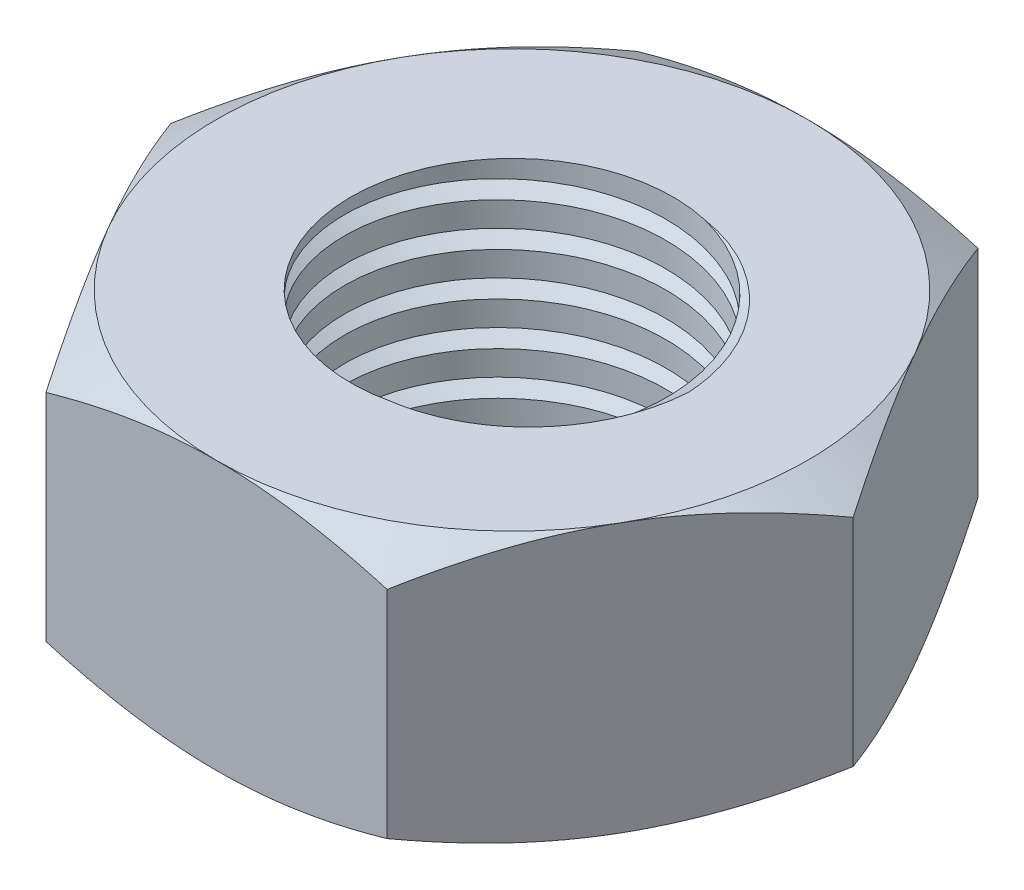
SolidWorks part; units mm, degrees
ref_plane "Front Plane" through (0, 0, 0) normal (0, 0, 1) x (1, 0, 0)
ref_plane "Top Plane" through (0, 0, 0) normal (0, 1, 0) x (1, 0, 0)
ref_plane "Right Plane" through (0, 0, 0) normal (1, 0, 0) x (0, 0, -1)
sketch "Sketch1" plane through (0, 0, 0) normal (0, 1, 0) x (1, 0, 0)
  line L0 (3.1754, 0) -> (1.5877, 2.75)
  line L1 (-3.1754, 0) -> (-1.5877, -2.75)
  line L2 (-1.5877, -2.75) -> (1.5877, -2.75)
  line L3 (1.5877, -2.75) -> (3.1754, 0)
  line L4 (1.5877, 2.75) -> (-1.5877, 2.75)
  line L5 (-1.5877, 2.75) -> (-3.1754, 0)
  circle A0 centre (0, 0) radius 2.75 construction
  dimension "D1" = 5.5
extrude "Boss-Extrude1" add sketch "Sketch1" along normal blind 2.5
sketch "Sketch2" plane through (0, 2.5, 0) normal (0, 1, 0) x (1, 0, 0)
  circle A0 centre (0, 0) radius 1.5
  dimension "D1" = 3
extrude "Cut-Extrude1" cut sketch "Sketch2" against normal blind 2.5
sketch "Sketch3" plane through (0, 2.5, 0) normal (0, 1, 0) x (1, 0, 0)
  circle A0 centre (0, 0) radius 2.75
  dimension "D1" = 5.5
extrude "Cut-Extrude3" cut sketch "Sketch3" against normal blind 0.5 draft 60 flip side to cut
sketch "Sketch4" plane through (0, 0, 0) normal (0, -1, 0) x (1, 0, 0)
  circle A0 centre (0, 0) radius 2.75
  dimension "D1" = 5.5
extrude "Cut-Extrude4" cut sketch "Sketch4" against normal blind 0.5 draft 60 flip side to cut
sketch "Sketch9" plane through (0, 2.5, 0) normal (0, 1, 0) x (1, 0, 0)
  circle A0 centre (0, 0) radius 1.5
  dimension "D1" = 3
curve "Helix/Spiral1" pitch 0.4 height 4 radius 1.5 centre (0, 2.5, 0) axis (0, -1, 0) start towards (1, 0, 0)
sketch3d "3DSketch1"
  line L0 (1.3528, -1.67, 0) -> (1.3528, -1.33, 0)
  line L1 (1.3528, -1.33, 0) -> (1.6472, -1.5, 0)
  line L2 (1.6472, -1.5, 0) -> (1.3528, -1.67, 0)
  dimension "D1" = 0.34
  dimension "D2" = 0.34
  dimension "D3" = 0.34
sweep "Cut-Sweep1" cut profiles "3DSketch1" path "Helix/Spiral1" align with end faces yes
